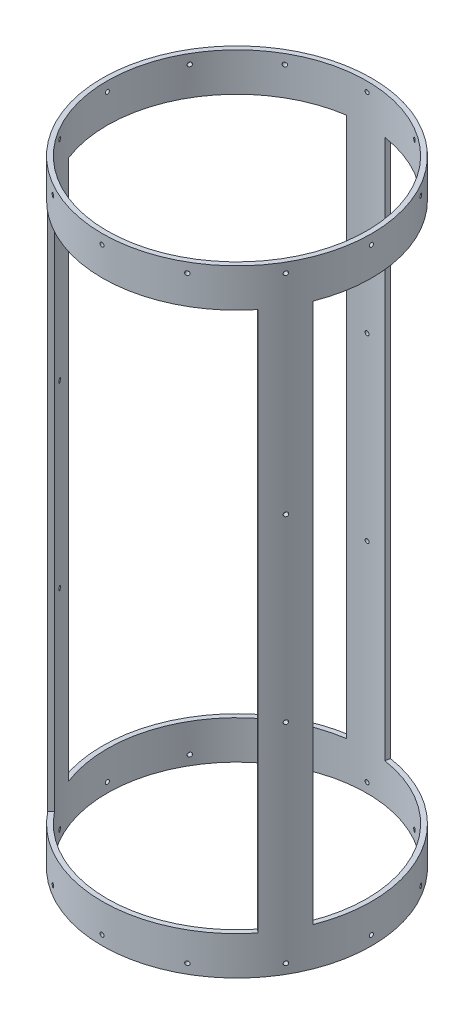
SolidWorks part; units mm, degrees
material "6061-T6 (SS)"
ref_plane "Front Plane" through (0, 0, 0) normal (0, 0, 1) x (1, 0, 0)
ref_plane "Top Plane" through (0, 0, 0) normal (0, 1, 0) x (1, 0, 0)
ref_plane "Right Plane" through (0, 0, 0) normal (1, 0, 0) x (0, 0, -1)
sketch "Sketch1" plane through (0, 0, 0) normal (0, 1, 0) x (1, 0, 0)
  circle A0 centre (0, 0) radius 88.9
  circle A1 centre (0, 0) radius 85.725
  dimension "D1" = 177.8
  dimension "D2" = 171.45
extrude "Boss-Extrude1" add sketch "Sketch1" along normal mid plane 407.162
sketch "Sketch6" plane through (0, -203.581, 0) normal (0, -1, 0) x (-1, 0, 0)
  line L0 (82.7901, -32.3885) -> (79.8333, -31.2317)
  line L1 (13.1222, 87.9262) -> (12.6536, 84.786)
  line L2 (0, 0) -> (0, 85.725) construction
  line L3 (-97.8543, 0) -> (97.8543, 0) construction
  line L4 (0, 0) -> (12.6536, 84.786) construction
  arc A0 (13.1222, 87.9262) -> (82.7901, -32.3885) centre (0, 0) cw
  circle A1 centre (0, 0) radius 88.9 construction
  arc A2 (12.6536, 84.786) -> (79.8333, -31.2317) centre (0, 0) cw
  circle A3 centre (0, 0) radius 85.725 construction
  arc A4 (0, 85.725) -> (12.6536, 84.786) centre (0, 0) cw construction
  dimension "D1" = 153.924
  dimension "D2" = 12.7
extrude "Cut-Extrude5" cut sketch "Sketch6" against normal offset from surface (356.362 mm away) 25.4 from offset 25.4 up to face at (0, 203.581, 88.9) offset against normal yes
pattern_circular "CirPattern5" count 3 over 360 about axis through (0, -203.581, 0) along (0, 1, 0) of "Cut-Extrude5"
ref_plane "Plane1" through (0, 0, -88.9) normal (0, 0, -1) x (-1, 0, 0)
sketch "Sketch3" plane through (0, 0, 0) normal (0, 0, -1) x (-1, 0, 0)
  line L1 (-88.9, -203.581) -> (88.9, -203.581) construction
  line L3 (-12.8692, 178.181) -> (-12.8692, -178.181) construction
  circle A0 centre (-0.1692, -197.231) radius 1.3525
  dimension "D1" = 6.35
  dimension "D2" = 2.7051
  dimension "D4" = 12.7
extrude "Cut-Extrude2" cut sketch "Sketch3" along normal up to surface (88.8921 mm away) up to face at (-0.0918, 0, 72.1578)
pattern_circular "CirPattern2" count 12 over 360 about axis through (0, 203.581, 0) along (0, -1, 0) of "Cut-Extrude2" reverse direction yes
sketch "Sketch4" plane through (0, 0, -88.9) normal (0, 0, -1) x (-1, 0, 0)
  line L1 (88.9, 203.581) -> (-88.9, 203.581) construction
  circle A0 centre (-0.1692, 197.231) radius 1.3525
  dimension "D1" = 2.7051
  dimension "D2" = 6.35
extrude "Cut-Extrude3" cut sketch "Sketch4" against normal blind 15.24
pattern_circular "CirPattern3" count 12 over 360 about axis through (0, 203.581, 0) along (0, 1, 0) of "Cut-Extrude3"
ref_plane "Plane2" through (0, 0, 88.9) normal (0, 0, 1) x (1, 0, 0)
sketch "Sketch5" plane through (0, 0, 88.9) normal (0, 0, 1) x (1, 0, 0)
  line L0 (-88.9, 178.181) -> (-13.1222, 178.181) construction
  line L1 (88.9, -178.181) -> (13.3458, -178.181) construction
  circle A0 centre (0.1692, 59.3937) radius 1.3526
  circle A1 centre (0.1692, -59.3937) radius 1.3526
  dimension "D1" = 118.7873
  dimension "D2" = 118.7873
  dimension "D3" = 2.7051
  dimension "D4" = 2.7051
extrude "Cut-Extrude4" cut sketch "Sketch5" against normal up to surface (177.787 mm away) up to face at (-77.2806, 196.6248, -43.9383)
pattern_circular "CirPattern4" count 3 over 360 about axis through (0, 203.581, 0) along (0, -1, 0) of "Cut-Extrude4"
